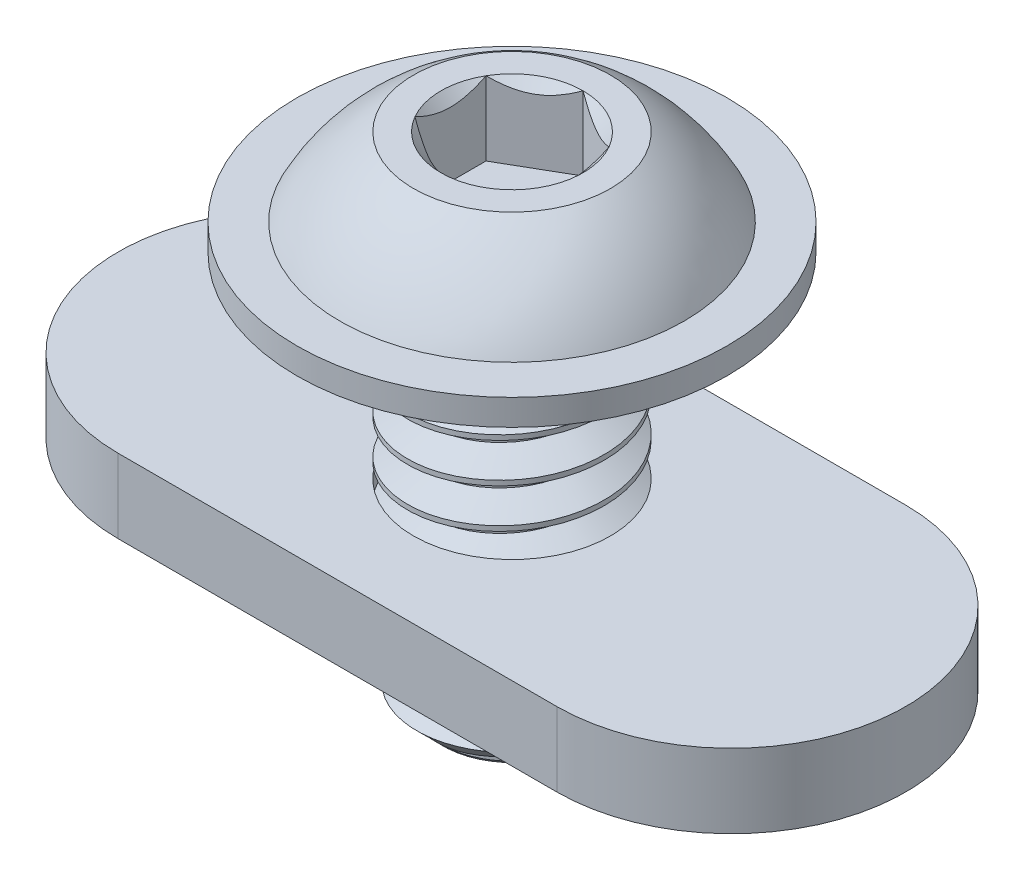
SolidWorks part; units mm, degrees
note: '?' marks a value the reader was unsure of.
ref_plane "Front Plane" through (0, 0, 0) normal (0, 0, 1) x (1, 0, 0)
ref_plane "Top Plane" through (0, 0, 0) normal (0, 1, 0) x (1, 0, 0)
ref_plane "Right Plane" through (0, 0, 0) normal (1, 0, 0) x (0, 0, -1)
sketch "Sketch1" plane through (0, 0, 0) normal (0, 1, 0) x (1, 0, 0)
  circle A0 centre (0, 0) radius 3.175
  point P3 (-3.175, 0)
  point P4 (3.175, 0)
  dimension "D1" = 6.35
extrude "Boss-Extrude1" add sketch "Sketch1" against normal blind 12.7
sketch "Sketch2" plane through (0, -12.7, 0) normal (0, -1, 0) x (1, 0, 0)
  circle A1 centre (0, 0) radius 3.175
  circle A2 centre (0, 0) radius 3.175
  point P0 (0, -3.175)
  dimension "D1" = 0
curve "Helix/Spiral1" pitch 1.27 height 13.97 turns 11
sketch "Sketch3" plane through (0, 0, 0) normal (1, 0, 0) x (0, 0, -1)
  line L0 (3.3125, -12.6206) -> (2.2126, -13.2556) construction
  line L1 (2.2126, -13.2556) -> (3.3125, -13.8906) construction
  line L2 (3.3125, -13.8906) -> (3.3125, -12.6206) construction
  line L3 (2.3501, -13.1762) -> (2.3501, -13.335) construction
  line L4 (3.175, -12.7) -> (3.175, -13.8112) construction
  line L5 (2.2126, -13.2556) -> (2.3501, -13.2556) construction
  line L6 (3.175, -13.2556) -> (3.3125, -13.2556) construction
  line L8 (2.2126, -13.2556) -> (-3.175, -13.2556) construction
  line L9 (2.3501, -13.1762) -> (3.2437, -12.6603)
  line L10 (2.3501, -13.1762) -> (2.3501, -13.335)
  line L11 (2.3501, -13.335) -> (3.2437, -13.8509)
  line L12 (3.2437, -13.8509) -> (3.2437, -12.6603)
  line L14 (-3.175, -13.2556) -> (-3.175, -11.9856) construction
  line L15 (-3.175, -11.9856) -> (-3.175, -10.7156) construction
  line L16 (-3.175, -10.7156) -> (-3.175, -9.4456) construction
  line L17 (-3.175, -9.4456) -> (-3.175, -8.1756) construction
  line L18 (-3.175, 0) -> (-3.175, -12.7) construction
  point P15 (3.2437, -13.2556)
  dimension "D1" = 1.27
  dimension "D2" = 0.1588
sweep "Cut-Sweep1" cut profiles "Sketch3" path "Helix/Spiral1" align with end faces yes
sketch "Sketch4" plane through (0, -12.7, 0) normal (0, -1, 0) x (1, 0, 0)
  circle A0 centre (0, 0) radius 2.2126
extrude "Cut-Extrude1" cut sketch "Sketch4" against normal blind 1.27 draft 45 flip side to cut
sketch "Sketch5" plane through (0, 0, 0) normal (0, 0, 1) x (1, 0, 0)
  line L0 (0, 0) -> (0, 3.3528)
  line L1 (-6.9342, 0) -> (0, 0)
  line L2 (0, 3.3528) -> (-3.175, 3.3528)
  line L3 (-5.5499, 0.8382) -> (-6.9342, 0.8382)
  line L4 (-6.9342, 0.8382) -> (-6.9342, 0)
  line L5 (0, 0) -> (0, -12.7) construction
  arc A0 (-3.175, 3.3528) -> (-5.5499, 0.8382) centre (0, -2.0246) ccw
  dimension "D1" = 3.3528
  dimension "D2" = 0.8382
  dimension "D3" = 13.8684
  dimension "D4" = 11.0998
revolve "Revolve1" add sketch "Sketch5" angle 360 mid plane about L0
sketch "Sketch6" plane through (0, 3.3528, 0) normal (0, 1, 0) x (1, 0, 0)
  line L1 (0, 2.2914) -> (-1.9844, 1.1457)
  line L2 (-1.9844, 1.1457) -> (-1.9844, -1.1457)
  line L3 (-1.9844, -1.1457) -> (0, -2.2914)
  line L4 (0, -2.2914) -> (1.9844, -1.1457)
  line L5 (1.9844, -1.1457) -> (1.9844, 1.1457)
  line L6 (1.9844, 1.1457) -> (0, 2.2914)
  circle A0 centre (0, 0) radius 1.9844 construction
  dimension "D1" = 3.9688
extrude "Cut-Extrude2" cut sketch "Sketch6" against normal blind 2.3813
sketch "Sketch7" plane through (0, 3.3528, 0) normal (0, 1, 0) x (1, 0, 0)
  circle A0 centre (0, 0) radius 2.2914
extrude "Cut-Extrude3" cut sketch "Sketch7" against normal blind 2.3813 draft 45
sketch "Sketch8" plane through (0, 0, 0) normal (0, 1, 0) x (1, 0, 0)
  line L0 (-7.0739, 0) -> (7.0739, 0) construction
  line L1 (-7.0739, 5.6261) -> (7.0739, 5.6261)
  line L2 (-7.0739, -5.6261) -> (7.0739, -5.6261)
  line L4 (-12.7, 5.6261) -> (12.7, 5.6261) construction
  line L5 (-12.7, 5.6261) -> (-12.7, -5.6261) construction
  line L6 (-12.7, -5.6261) -> (12.7, -5.6261) construction
  line L7 (12.7, 5.6261) -> (12.7, -5.6261) construction
  arc A0 (-7.0739, 5.6261) -> (-7.0739, -5.6261) centre (-7.0739, 0) ccw
  arc A1 (7.0739, -5.6261) -> (7.0739, 5.6261) centre (7.0739, 0) ccw
  circle A3 centre (0, 0) radius 3.175
  circle A4 centre (0, 0) radius 3.175
  point P2 (0, 0)
  dimension "D2" = 25.4
  dimension "D3" = 11.2522
  dimension "D1" = 0
extrude "Boss-Extrude2" add sketch "Sketch8" against normal blind 2.3876 from offset 6.35 separate body offset against normal yes
sketch "Sketch9" plane through (0, -8.7376, 0) normal (0, -1, 0) x (1, 0, 0)
  circle A1 centre (0, 0) radius 3.175 construction
  circle A2 centre (0, 0) radius 3.175
  circle A3 centre (0, 0) radius 3.5687
  dimension "D1" = 7.1374
extrude "Boss-Extrude3" add sketch "Sketch9" along normal blind 0.762
sketch "SketchZ" plane through (0, 0, 0) normal (0, 0, 1) x (1, 0, 0)
  line L0 (3.175, -12.9381) -> (3.175, -11.6681) construction
  line L2 (0, -13.2556) -> (0, -11.9856) construction
  line L4 (3.175, -12.9381) -> (0, -12.9381) construction
  line L5 (0, -9.4456) -> (0, -8.1756) construction
  line L6 (0, -12.6206) -> (0, -13.2556) construction
ref_axis "Axis1" through (0, 0.8382, 0) along (0, -1, 0)?
equation "\"D3@Helix/Spiral1\" = \"D4@Helix/Spiral1\" + \"D1@Boss-Extrude1\""
equation "\"D1@Sketch3\" = \"D4@Helix/Spiral1\""
equation "\"D2@Sketch3\" = \"D1@Sketch3\" / 8"
equation "\"D1@Cut-Extrude1\" = \"D4@Helix/Spiral1\""
equation "\"D1@Cut-Extrude2\" = \"D1@Sketch6\" * 3/5"
equation "\"D1@Cut-Extrude3\" = \"D1@Cut-Extrude2\""
equation "\"D2@Sketch5\" = \"D1@Sketch5\" * 1/4"
